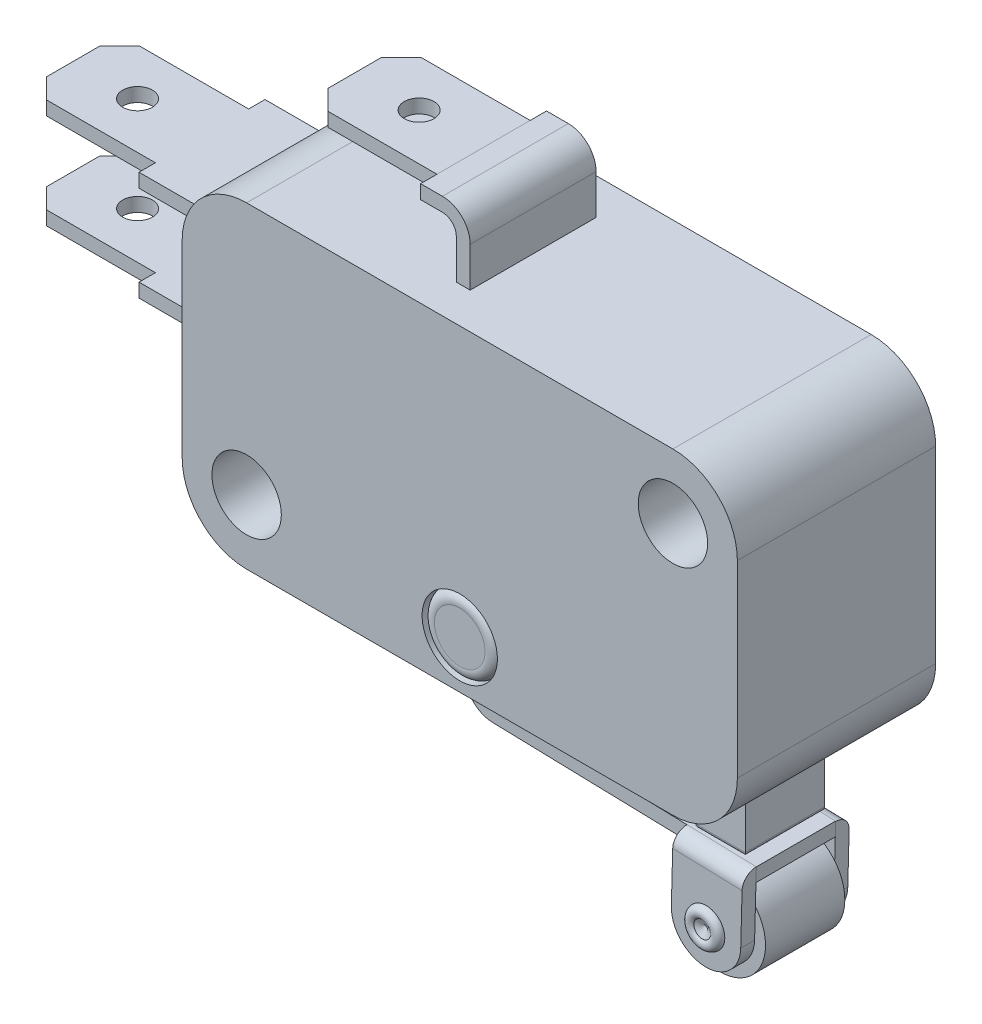
SolidWorks part; units mm, degrees
material "ABS"
ref_plane "Plan de face" through (0, 0, 0) normal (0, 0, 1) x (1, 0, 0)
ref_plane "Plan de dessus" through (0, 0, 0) normal (0, 1, 0) x (1, 0, 0)
ref_plane "Plan de droite" through (0, 0, 0) normal (1, 0, 0) x (0, 0, -1)
ref_plane "Plan1" through (-2, 0, 0) normal (1, 0, 0) x (0, 0, -1)
sketch "Esquisse1" plane through (0, 0, 0) normal (0, 0, 1) x (1, 0, 0)
  line L1 (10.75, -8) -> (-10.75, -8)
  line L2 (14, -4.75) -> (14, 4.75)
  line L3 (10.75, 8) -> (-10.75, 8)
  line L4 (-14, -4.75) -> (-14, 4.75)
  line L5 (14, -8) -> (-14, 8) construction
  line L6 (14, 8) -> (-14, -8) construction
  circle A0 centre (10.75, 4.75) radius 1.75
  circle A1 centre (-10.75, -4.75) radius 1.75
  circle A2 centre (10.75, 4.75) radius 3.25 construction
  circle A3 centre (-10.75, -4.75) radius 3.25 construction
  arc A4 (-10.75, 8) -> (-14, 4.75) centre (-10.75, 4.75) ccw
  arc A5 (-10.75, -8) -> (-14, -4.75) centre (-10.75, -4.75) cw
  arc A6 (10.75, -8) -> (14, -4.75) centre (10.75, -4.75) ccw
  arc A7 (14, 4.75) -> (10.75, 8) centre (10.75, 4.75) ccw
  circle A8 centre (0, -5.6) radius 1.9
  point P0 (0, 0)
  dimension "D1" = 3.5
  dimension "D5" = 3.25
  dimension "D7" = 6.5
  dimension "D8" = 6.5
  dimension "D9" = 3.25
  dimension "D10" = 3.8
  dimension "D2" = 24.75
  dimension "D3" = 3.25
  dimension "D4" = 3.25
  dimension "D6" = 3.25
  dimension "D11" = 2.4
extrude "Boss.-Extru.1" add sketch "Esquisse1" against normal blind 10
sketch "Esquisse2" plane through (0, 0, 0) normal (0, 0, 1) x (1, 0, 0)
  line L0 (-10.75, -1.5) -> (-14, -1.5) construction
  line L1 (-14, -4.75) -> (-14, 4.75) construction
  line L2 (-8.5, -4.75) -> (-8.5, -8) construction
  line L3 (10.75, -8) -> (-10.75, -8) construction
  line L4 (-10.75, -2.5) -> (-14, -2.5) construction
  line L5 (10.75, 2.5) -> (14, 2.5) construction
  line L6 (14, -4.75) -> (14, 4.75) construction
  line L7 (8.5, 4.75) -> (8.5, 8) construction
  line L8 (10.75, 8) -> (-10.75, 8) construction
  line L9 (-10.75, 8) -> (8.5, 8)
  line L10 (8.5, 8) -> (8.5, 4.75)
  line L11 (10.75, 2.5) -> (14, 2.5)
  line L12 (14, 2.5) -> (14, -4.75)
  line L13 (10.75, -8) -> (-8.5, -8)
  line L14 (-8.5, -8) -> (-8.5, -4.75)
  line L15 (-14, 4.75) -> (-14, -2.5)
  line L16 (-14, -2.5) -> (-10.75, -2.5)
  circle A0 centre (10.75, 4.75) radius 2.25 construction
  circle A1 centre (-10.75, -4.75) radius 2.25 construction
  circle A2 centre (-10.75, -4.75) radius 3.25 construction
  arc A3 (-14, 4.75) -> (-10.75, 8) centre (-10.75, 4.75) cw
  arc A4 (8.5, 4.75) -> (10.75, 2.5) centre (10.75, 4.75) ccw
  arc A5 (14, -4.75) -> (10.75, -8) centre (10.75, -4.75) cw
  arc A6 (-8.5, -4.75) -> (-10.75, -2.5) centre (-10.75, -4.75) ccw
  dimension "D1" = 4.5
extrude "Enlèv. mat.-Extru.1" cut sketch "Esquisse2" against normal blind 3
sketch "Esquisse9" plane through (0, 0, -3) normal (0, 0, 1) x (1, 0, 0)
  line L0 (-8.5, -8) -> (10.75, -8) construction
  line L2 (8.9, -8) -> (8.9, -11)
  line L3 (8.9, -11) -> (11.4, -11)
  line L4 (11.4, -8) -> (11.4, -11)
  line L5 (14, -4.75) -> (14, 2.5) construction
  line L8 (11.4, -8) -> (11.4, -7)
  line L9 (11.4, -7) -> (8.9, -7)
  line L10 (8.9, -8) -> (8.9, -7)
  dimension "D1" = 2.6
  dimension "D2" = 2.5
  dimension "D3" = 3
  dimension "D4" = 4
extrude "Boss.-Extru.6" add sketch "Esquisse9" against normal blind 4 separate body
fillet "Congé1" radius 0.2 4 edges at (11.4, -11, -5) (10.15, -11, -7) (8.9, -11, -5) (10.15, -11, -3)
sketch "Esquisse10" plane through (0, 0, -3) normal (0, 0, 1) x (1, 0, 0)
  line L0 (-1.8993, -5.5492) -> (-2.0203, -10.0728)
  line L1 (-1.3393, -10.7912) -> (11.956, -11.1468)
  line L2 (-1.8993, -5.5492) -> (-2.5991, -5.5305)
  line L3 (-2.5991, -5.5305) -> (-2.72, -10.054)
  line L4 (-1.358, -11.491) -> (11.9373, -11.8465)
  line L5 (11.956, -11.1468) -> (11.9373, -11.8465)
  arc A1 (-2.72, -10.054) -> (-1.358, -11.491) centre (-1.3205, -10.0915) ccw
  arc A2 (-2.0203, -10.0728) -> (-1.3393, -10.7912) centre (-1.3205, -10.0915) ccw
  point P13 (-2.039, -10.7725)
  dimension "D6" = 0.7
  dimension "D1" = 90
  dimension "D2" = 0.7
  dimension "D3" = 14
  dimension "D5" = 0.7
  dimension "D7" = 4.5235
extrude "Boss.-Extru.7" add sketch "Esquisse10" against normal blind 4
sketch "Esquisse11" plane through (12.2453, -0.3275, 0) normal (0.9996, -0.0267, 0) x (0, 0, -1)
  line L0 (7, -11.5232) -> (7, -10.8232) construction
  line L1 (3, -10.8232) -> (2.3, -10.8232)
  line L2 (3, -10.8232) -> (3, -15.8232)
  line L3 (3, -15.8232) -> (2.3, -15.8232)
  line L4 (2.3, -10.8232) -> (2.3, -15.8232)
  line L5 (7, -10.8439) -> (7.7, -10.8439)
  line L6 (7, -10.8439) -> (7, -15.8439)
  line L7 (7, -15.8439) -> (7.7, -15.8439)
  line L8 (7.7, -10.8439) -> (7.7, -15.8439)
extrude "Boss.-Extru.8" add sketch "Esquisse11" against normal blind 3.5 separate body
fillet "Congé2" radius 1.75 2 edges at (8.3236, -16.0514, -2.65) (11.8223, -16.145, -2.65)
fillet "Congé3" radius 1.75 2 edges at (11.8218, -16.1657, -7.35) (8.323, -16.0722, -7.35)
fillet "Congé4" radius 0.7 1 edges at (10.2066, -11.1, -2.3)
fillet "Congé5" radius 0.7 1 edges at (10.2061, -11.1207, -7.7)
sketch "Esquisse12" plane through (0, 0, -2.3) normal (0, 0, 1) x (1, 0, 0)
  circle A0 centre (10.1197, -14.3488) radius 0.75
  dimension "D1" = 1.5
extrude "Enlèv. mat.-Extru.2" cut sketch "Esquisse12" against normal through all
sketch "Esquisse13" plane through (0, 0, -7) normal (0, 0, 1) x (1, 0, 0)
  circle A0 centre (10.1197, -14.3488) radius 2.3
  dimension "D1" = 4.6
extrude "Boss.-Extru.9" add sketch "Esquisse13" along normal blind 4 separate body
ref_plane "Plan2" through (10.496, -0.2807, 0) normal (0.9996, -0.0267, 0) x (0, 0, -1)
sketch "Esquisse14" plane through (10.496, -0.2807, 0) normal (0.9996, -0.0267, 0) x (0, 0, -1)
  line L0 (2.3, -13.3232) -> (7.7, -13.3232)
  line L1 (7.7, -13.3232) -> (7.7, -13.1239)
  line L2 (7.7, -14.0939) -> (7.7, -11.5439) construction
  line L3 (2.3, -13.3232) -> (2.3, -13.1239)
  line L4 (2.3, -11.5232) -> (2.3, -14.0732) construction
  line L5 (2.1094, -13.6545) -> (2.3, -14.0732)
  line L6 (2.3, -14.0732) -> (7.7, -14.0939)
  line L7 (7.7, -14.0939) -> (7.9042, -13.6545)
  arc A0 (2.3, -13.1239) -> (2.1094, -13.6545) centre (2.3, -13.4235) ccw
  arc A1 (7.7, -13.1239) -> (7.9042, -13.6545) centre (7.7, -13.4285) cw
revolve "Révolution3" add sketch "Esquisse14" angle 360 about L6
sketch "Esquisse3" plane through (0, 0, -3) normal (0, 0, 1) x (1, 0, 0)
  line L0 (-14, 4.75) -> (-14, -2.5)
  line L1 (-14, -2.5) -> (-10.75, -2.5)
  line L2 (-8.5, -4.75) -> (-8.5, -8)
  line L3 (-8.5, -8) -> (10.75, -8)
  line L4 (14, -4.75) -> (14, 2.5)
  line L5 (14, 2.5) -> (10.75, 2.5)
  line L6 (8.5, 4.75) -> (8.5, 8)
  line L7 (8.5, 8) -> (-10.75, 8)
  arc A0 (-8.5, -4.75) -> (-10.75, -2.5) centre (-10.75, -4.75) ccw construction
  arc A1 (-10.75, 8) -> (-14, 4.75) centre (-10.75, 4.75) ccw
  arc A2 (-10.75, -2.5) -> (-8.5, -4.75) centre (-10.75, -4.75) cw
  arc A3 (10.75, -8) -> (14, -4.75) centre (10.75, -4.75) ccw
  arc A4 (10.75, 2.5) -> (8.5, 4.75) centre (10.75, 4.75) cw
  circle A5 centre (0, -5.6) radius 1.9
  dimension "D1" = 3.8
extrude "Boss.-Extru.2" add sketch "Esquisse3" along normal blind 3 separate body
sketch "Esquisse5" plane through (0, 0, 0) normal (1, 0, 0) x (0, 0, -1)
  line L0 (0.5, -3.714) -> (9.5, -3.714)
  line L1 (0, -4.75) -> (0, 2.5) construction
  line L2 (10, -4.75) -> (10, 4.75) construction
  line L3 (10, -4.75) -> (3, -4.75) construction
  line L4 (0, -4.3236) -> (0, -5.6)
  line L5 (0, -5.6) -> (9.5, -5.6)
  line L6 (5.0564, -5.6) -> (15.7356, -5.6) construction
  line L7 (9.5, -5.6) -> (9.5, -4.75)
  arc A0 (0.5, -3.714) -> (0, -4.3236) centre (0.5, -4.2238) ccw
  arc A1 (9.5, -3.714) -> (9.5, -4.75) centre (9.5, -4.232) cw
  dimension "D1" = 5.6
  dimension "D2" = 0.5
  dimension "D3" = 0.5
revolve "Révolution1" add sketch "Esquisse5" angle 360 about L6
sketch "Esquisse6" plane through (0, 0, 0) normal (0, 1, 0) x (1, 0, 0)
  line L0 (18.9138, 5) -> (-22.3944, 5) construction
  line L1 (10.75, 10) -> (-10.75, 10) construction
  line L2 (-14, 8.175) -> (-18, 8.175)
  line L3 (-14, 10) -> (-14, 3) construction
  line L4 (-18, 8.175) -> (-18, 7.35)
  line L5 (-18, 7.35) -> (-23.5, 7.35)
  line L6 (-23.5, 7.35) -> (-24.5, 6.35)
  line L7 (-24.5, 6.35) -> (-24.5, 3.65)
  line L8 (-14, 8.175) -> (-14, 1.825)
  line L9 (-14, 1.825) -> (-18, 1.825)
  line L10 (-18, 1.825) -> (-18, 2.65)
  line L11 (-18, 2.65) -> (-23.5, 2.65)
  line L12 (-23.5, 2.65) -> (-24.5, 3.65)
  circle A0 centre (-21.25, 5) radius 0.75
  point P16 (-14, 5)
  point P20 (-24.5, 5)
  dimension "D5" = 1.5
  dimension "D1" = 5
  dimension "D2" = 3.175
  dimension "D3" = 4
  dimension "D4" = 6.5
  dimension "D6" = 3.25
  dimension "D7" = 1
  dimension "D8" = 2.35
  dimension "D9" = 1
extrude "Boss.-Extru.3" add sketch "Esquisse6" against normal blind 0.7 separate body
pattern_linear "Répétition linéaire1" count 2 spacing 4.8 along (0, 1, 0) of "Boss.-Extru.3"
sketch "Esquisse7" plane through (0, 0, -1.825) normal (0, 0, 1) x (1, 0, 0)
  line L0 (-2, 8) -> (-2, 10)
  line L1 (-2, -5.5153) -> (-2, 5.5153) construction
  line L2 (10.75, 8) -> (-10.75, 8) construction
  line L3 (-2.7, 10.7) -> (-3.8, 10.7)
  line L4 (-3.8, 10.7) -> (-3.8, 11.4)
  line L5 (-3.8, 11.4) -> (-2.7, 11.4)
  line L6 (-1.3, 10) -> (-1.3, 8)
  line L7 (-1.3, 8) -> (-2, 8)
  arc A0 (-2, 10) -> (-2.7, 10.7) centre (-2.7, 10) ccw
  arc A1 (-2.7, 11.4) -> (-1.3, 10) centre (-2.7, 10) cw
  point P12 (-2, 10.7)
  dimension "D5" = 0.7
  dimension "D6" = 1.4
  dimension "D1" = 0.7
  dimension "D2" = 0.7
  dimension "D3" = 2.7
  dimension "D4" = 2.5
extrude "Boss.-Extru.4" add sketch "Esquisse7" against normal blind 6.35 separate body
sketch "Esquisse8" plane through (0, 11.4, 0) normal (0, 1, 0) x (1, 0, 0)
  line L0 (-32.8098, 7.35) -> (21.89, 7.35) construction
  line L1 (-32.7173, 2.65) -> (21.9825, 2.65) construction
  line L2 (-3.8, 7.35) -> (-9.3, 7.35)
  line L3 (-10.3, 6.35) -> (-10.3, 3.65)
  line L4 (-9.3, 2.65) -> (-3.8, 2.65)
  line L5 (-3.8, 2.65) -> (-3.8, 7.35)
  line L6 (-32.8098, 5) -> (21.89, 5) construction
  line L7 (-9.3, 7.35) -> (-10.3, 6.35)
  line L8 (-10.3, 3.65) -> (-9.3, 2.65)
  line L10 (-3.8, 8.175) -> (-3.8, 1.825) construction
  circle A0 centre (-7.05, 5) radius 0.75
  point P6 (-10.3, 7.35)
  point P8 (-10.3, 2.65)
  dimension "D1" = 1.5
  dimension "D2" = 6.5
  dimension "D3" = 3.25
extrude "Boss.-Extru.5" add sketch "Esquisse8" against normal blind 0.7 separate body
equation "\"D5@Esquisse1\"=\"D3@Esquisse1\""
equation "\"D4@Esquisse1\"=\"D3@Esquisse1\""
equation "\"D6@Esquisse1\"=\"D3@Esquisse1\""
equation "\"D9@Esquisse6\"=\"D7@Esquisse6\""
equation "\"D5@Esquisse10\" = \"D2@Esquisse10\""
